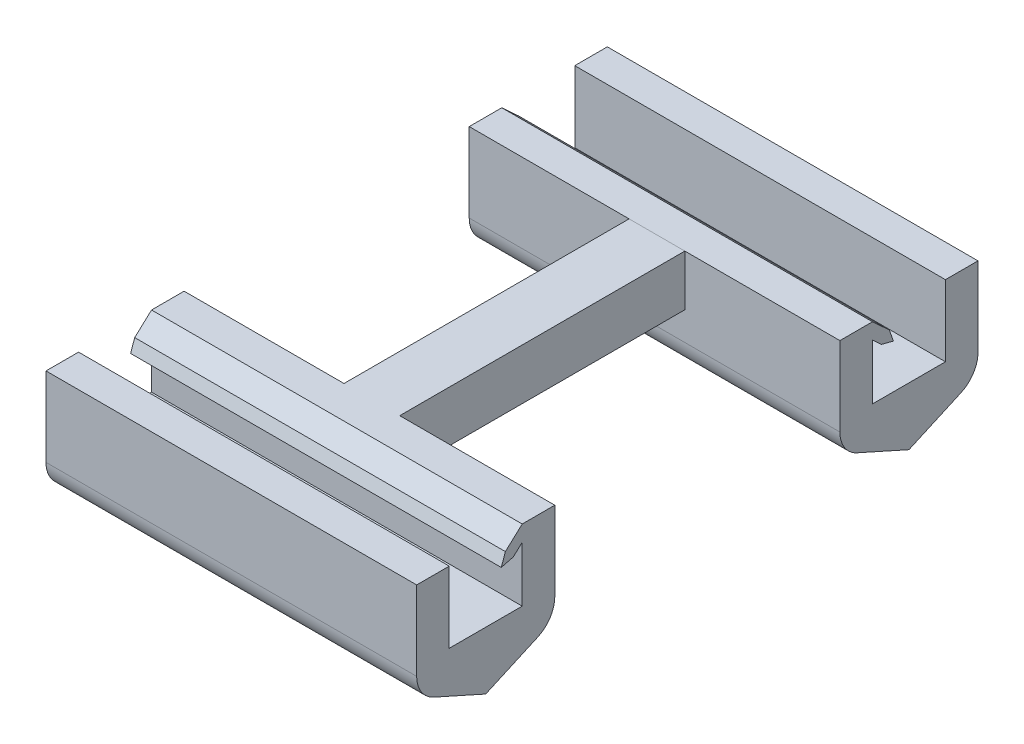
SolidWorks part; units mm, degrees
ref_plane "Front Plane" through (0, 0, 0) normal (0, 0, 1) x (1, 0, 0)
ref_plane "Top Plane" through (0, 0, 0) normal (0, 1, 0) x (1, 0, 0)
ref_plane "Right Plane" through (0, 0, 0) normal (1, 0, 0) x (0, 0, -1)
sketch "Sketch1" plane through (0, 0, 0) normal (1, 0, 0) x (0, 0, -1)
  line L0 (0, 0) -> (0, 50000) construction
  line L1 (6, -0.5435) -> (6, 0) construction
  line L2 (6.717, -0.9314) -> (6.4415, -0.6779) construction
  line L3 (6.5769, -0.5307) -> (6.3061, -0.8251) construction
  line L4 (6.3061, -0.8251) -> (6, -0.5435)
  line L5 (6.717, -0.9314) -> (6.3061, -0.8251)
  line L6 (6.5769, -0.5307) -> (6.717, -0.9314)
  line L7 (6, 0) -> (6.5769, -0.5307)
  line L8 (4.8841, 0) -> (4.8841, -2.7135)
  line L9 (5.4755, -3.6262) -> (7.25, -4.4206)
  line L10 (7.25, -1.3683) -> (7.25, 49998.6317) construction
  line L11 (-7.25, -1.3683) -> (-7.25, 49998.6317) construction
  line L12 (-6, 0) -> (-4.8841, 0)
  line L13 (-6, -2.4374) -> (-6, -0.5435)
  line L14 (-8.5, -2.4374) -> (-6, -2.4374)
  line L15 (-9.0245, -3.6262) -> (-7.25, -4.4206)
  line L16 (-9.6159, 0) -> (-9.6159, -2.7135)
  line L17 (-8.5, -2.4374) -> (-8.5, 0)
  line L18 (-8.5, 0) -> (-9.6159, 0)
  line L19 (-5.4755, -3.6262) -> (-7.25, -4.4206)
  line L20 (-4.8841, 0) -> (-4.8841, -2.7135)
  line L21 (-6, 0) -> (-6.5769, -0.5307)
  line L22 (-6.5769, -0.5307) -> (-6.717, -0.9314)
  line L23 (-6.717, -0.9314) -> (-6.3061, -0.8251)
  line L24 (-6.3061, -0.8251) -> (-6, -0.5435)
  line L25 (-6.5769, -0.5307) -> (-6.3061, -0.8251) construction
  line L26 (-6.717, -0.9314) -> (-6.4415, -0.6779) construction
  line L27 (-6, -0.5435) -> (-6, 0) construction
  line L28 (8.5, 0) -> (9.6159, 0)
  line L29 (8.5, -2.4374) -> (8.5, 0)
  line L30 (9.6159, 0) -> (9.6159, -2.7135)
  line L31 (9.0245, -3.6262) -> (7.25, -4.4206)
  line L32 (8.5, -2.4374) -> (6, -2.4374)
  line L33 (6, -2.4374) -> (6, -0.5435)
  line L34 (6, 0) -> (4.8841, 0)
  arc A0 (-5.4755, -3.6262) -> (-4.8841, -2.7135) centre (-5.8841, -2.7135) ccw
  arc A1 (-9.0245, -3.6262) -> (-9.6159, -2.7135) centre (-8.6159, -2.7135) cw
  arc A2 (9.0245, -3.6262) -> (9.6159, -2.7135) centre (8.6159, -2.7135) ccw
  arc A3 (5.4755, -3.6262) -> (4.8841, -2.7135) centre (5.8841, -2.7135) cw
  point P27 (-4.8841, -3.3614)
  point P35 (-6, -0.4524)
  point P45 (4.8841, -3.3614)
  dimension "D3" = 1
  dimension "D1" = 12
  dimension "D4" = 0.4
extrude "Boss-Extrude1" add sketch "Sketch1" along normal blind 12.7
sketch "Sketch2" plane through (0, 0, -4.8841) normal (0, 0, 1) x (1, 0, 0)
  line L1 (5.4781, 0) -> (7.3878, 0)
  line L2 (5.4781, 0) -> (5.4781, -1.7417)
  line L3 (5.4781, -1.7417) -> (7.3878, -1.7417) construction
  line L4 (7.3878, 0) -> (7.3878, -1.7417)
  line L5 (5.4781, -1.7417) -> (6.433, -2.6965)
  line L6 (6.433, -2.6965) -> (7.3878, -1.7417)
  line L7 (12.7, 0) -> (0, 0) construction
extrude "Boss-Extrude2" add sketch "Sketch2" along normal up to next
